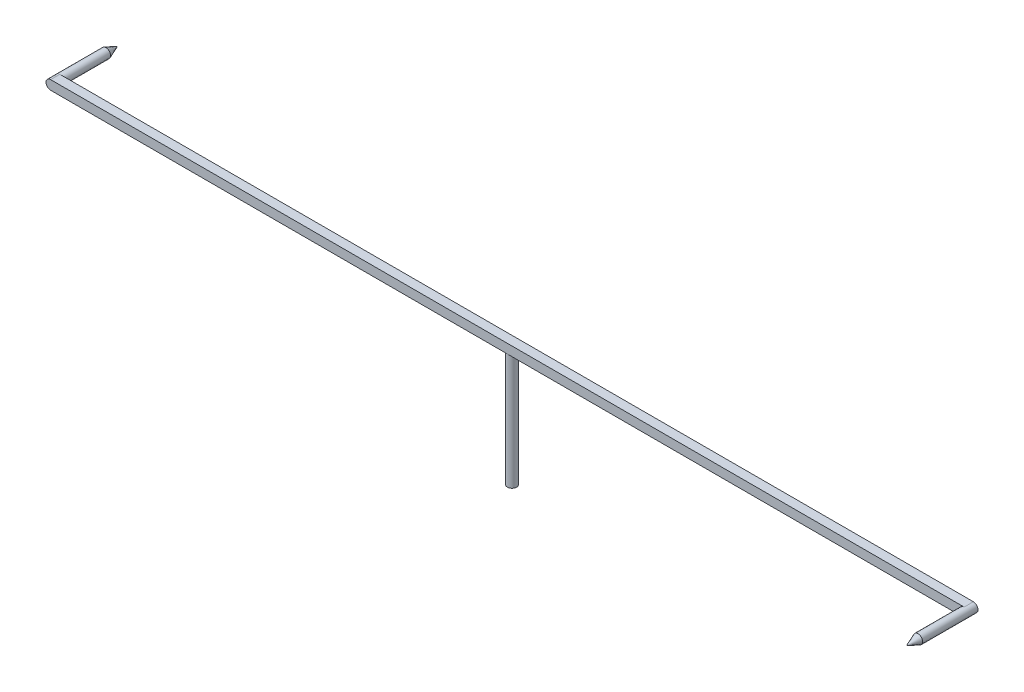
SolidWorks part; units mm, degrees
ref_plane "前视基准面" through (0, 0, 0) normal (0, 0, 1) x (1, 0, 0)
ref_plane "上视基准面" through (0, 0, 0) normal (0, 1, 0) x (1, 0, 0)
ref_plane "右视基准面" through (0, 0, 0) normal (1, 0, 0) x (0, 0, -1)
sketch "草图1" plane through (0, 0, 0) normal (0, 1, 0) x (1, 0, 0)
  circle A0 centre (0, 0) radius 0.4
  dimension "D1" = 0.8
extrude "凸台-拉伸1" add sketch "草图1" along normal blind 10
sketch "草图2" plane through (0, 10, 0) normal (0, 1, 0) x (1, 0, 0)
  line L1 (-40, 0.4) -> (40, 0.4)
  line L2 (-40, 0.4) -> (-40, -0.4)
  line L3 (-40, -0.4) -> (40, -0.4)
  line L4 (40, 0.4) -> (40, -0.4)
  circle A0 centre (0, 0) radius 0.4 construction
  dimension "D1" = 40
  dimension "D2" = 40
extrude "凸台-拉伸2" add sketch "草图2" along normal blind 0.8
fillet "圆角1" radius 0.4 4 edges at (40, 10, 0) (40, 10.8, 0) (-40, 10, 0) (-40, 10.8, 0)
sketch "草图3" plane through (0, 0, 0.4) normal (0, 0, 1) x (1, 0, 0)
  circle A0 centre (39.6, 10.4) radius 0.4
  dimension "D1" = 0.8
extrude "凸台-拉伸3" add sketch "草图3" along normal blind 4
sketch "草图4" plane through (0, 0, -0.4) normal (0, 0, -1) x (-1, 0, 0)
  circle A0 centre (39.6, 10.4) radius 0.4
  dimension "D1" = 0.8
extrude "凸台-拉伸4" add sketch "草图4" along normal blind 4
ref_plane "基准面1" through (0, 10.4, 0) normal (0, 1, 0) x (1, 0, 0)
sketch "草图5" plane through (0, 10.4, 0) normal (0, 1, 0) x (1, 0, 0)
  line L0 (39.6, -4.4) -> (39.6, -5.4)
  line L1 (39.2, -4.4) -> (40, -4.4) construction
  line L2 (40, -4.4) -> (39.6, -5.4)
  line L3 (39.6, -4.4) -> (40, -4.4)
  dimension "D1" = 1
revolve "旋转1" add sketch "草图5" angle 360 about L0
sketch "草图6" plane through (0, 10.4, 0) normal (0, 1, 0) x (1, 0, 0)
  line L0 (-39.6, 4.4) -> (-39.6, 5.4)
  line L1 (-39.2, 4.4) -> (-40, 4.4) construction
  line L2 (-39.6, 5.4) -> (-40, 4.4)
  line L3 (-40, 4.4) -> (-39.6, 4.4)
  dimension "D1" = 1
revolve "旋转2" add sketch "草图6" angle 360 about L0
